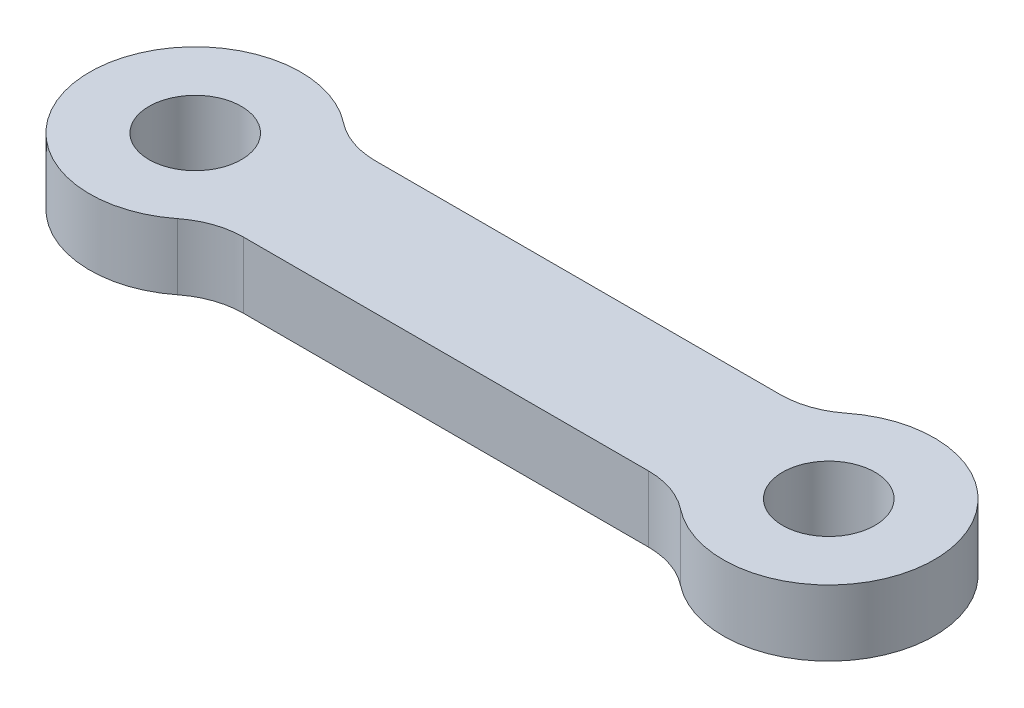
SolidWorks part; units mm, degrees
ref_plane "Front Plane" through (0, 0, 0) normal (0, 0, 1) x (1, 0, 0)
ref_plane "Top Plane" through (0, 0, 0) normal (0, 1, 0) x (1, 0, 0)
ref_plane "Right Plane" through (0, 0, 0) normal (1, 0, 0) x (0, 0, -1)
sketch "Sketch1" plane through (0, 0, 0) normal (0, 1, 0) x (1, 0, 0)
  line L0 (0, 0) -> (24, 0) construction
  line L1 (3.1225, 2.5) -> (20.8775, 2.5)
  line L2 (3.1225, -2.5) -> (20.8775, -2.5)
  circle A0 centre (0, 0) radius 4
  circle A1 centre (24, 0) radius 4
  circle A2 centre (0, 0) radius 1.75
  circle A3 centre (24, 0) radius 1.75
  dimension "D1" = 8
  dimension "D3" = 8
  dimension "D5" = 3.5
  dimension "D6" = 3.5
  dimension "D2" = 24
  dimension "D4" = 2.5
extrude "Boss-Extrude1" add sketch "Sketch1" along normal blind 2.5 contours A2 A0 | L0 A0 L2 A1 | A0 L0 A1 L1 | A1 A3 region at (3.6675, 0, 1.2873) region at (12, 0, -1.2715) region at (12, 0, 1.2715) region at (20.3325, 0, -1.2873)
fillet "Fillet1" radius 3 4 edges at (3.1225, 1.25, 2.5) (20.8775, 1.25, 2.5) (20.8775, 1.25, -2.5) (3.1225, 1.25, -2.5)
